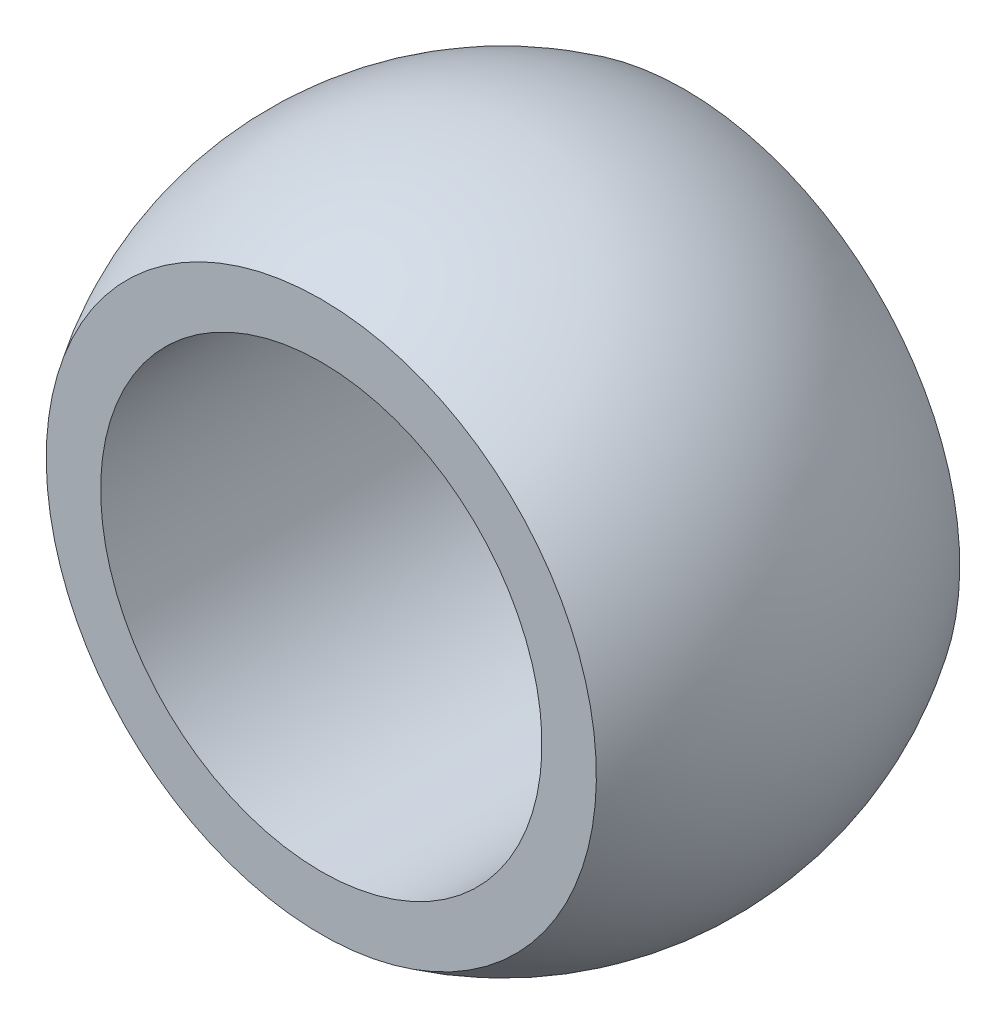
SolidWorks part; units mm, degrees
material "Plain Carbon Steel"
ref_plane "Front Plane" through (0, 0, 0) normal (0, 0, 1) x (1, 0, 0)
ref_plane "Top Plane" through (0, 0, 0) normal (0, 1, 0) x (1, 0, 0)
ref_plane "Right Plane" through (0, 0, 0) normal (1, 0, 0) x (0, 0, -1)
sketch "Sketch1" plane through (0, 0, 0) normal (1, 0, 0) x (0, 0, -1)
  line L0 (9.5416, 0) -> (-9.5416, 0) construction
  line L1 (7, 8.5) -> (-7, 8.5)
  line L2 (-7, 8.5) -> (-7, 10.5967)
  line L3 (7, 8.5) -> (7, 10.5967)
  arc A0 (7, 10.5967) -> (-7, 10.5967) centre (0, 0) ccw
  point P3 (0, 8.5)
  dimension "D1" = 8.5
  dimension "D3" = 12.7
  dimension "D2" = 14
revolve "Revolve1" add sketch "Sketch1"
sketch "Sketch2" plane through (0, 0, 0) normal (1, 0, 0) x (0, 0, -1)
  line L0 (0, 16.302) -> (0, -16.302) construction
  line L1 (-11.2912, 0) -> (11.2912, 0) construction
  point P5 (0, 0)
